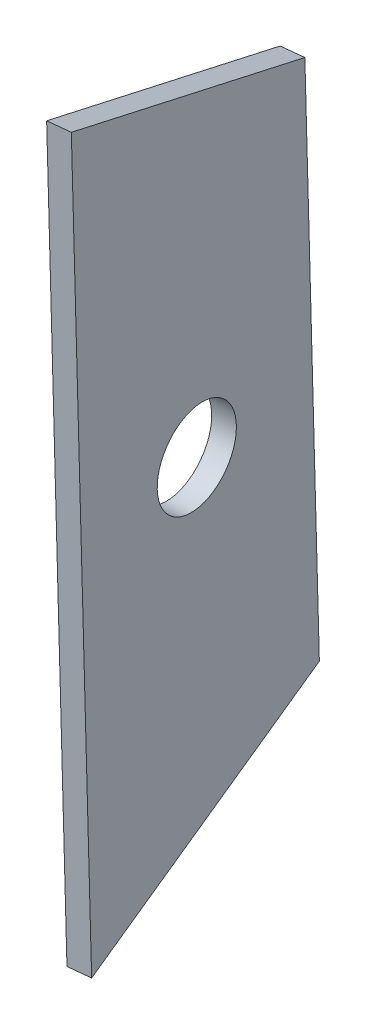
SolidWorks part; units mm, degrees
ref_plane "Front Plane" through (0, 0, 0) normal (0, 0, 1) x (1, 0, 0)
ref_plane "Top Plane" through (0, 0, 0) normal (0, 1, 0) x (1, 0, 0)
ref_plane "Right Plane" through (0, 0, 0) normal (1, 0, 0) x (0, 0, -1)
sketch "Sketch1" plane through (368.9369, -5.3839, -45.5872) normal (0.9923, -0.0145, -0.1226) x (-0.1226, 0.0018, -0.9925)
  line L0 (411.5941, 245.558) -> (414.1809, 191.185)
  line L1 (90.3213, 348.9052) -> (472.4727, 225.9745) construction
  line L2 (183.6443, 75.6122) -> (478.9871, 223.6738) construction
  line L3 (414.1809, 191.185) -> (432.7973, 200.5179)
  line L4 (432.7973, 200.5179) -> (430.9508, 239.3313)
  line L5 (430.9508, 239.3313) -> (411.5941, 245.558)
  line L6 (412.8875, 218.3715) -> (431.8741, 219.9246) construction
  circle A0 centre (422.3808, 219.1481) radius 3.2639
  dimension "D1" = 6.5278
  dimension "D2" = 19.05
extrude "Boss-Extrude1" add sketch "Sketch1" along normal blind 1.5875
